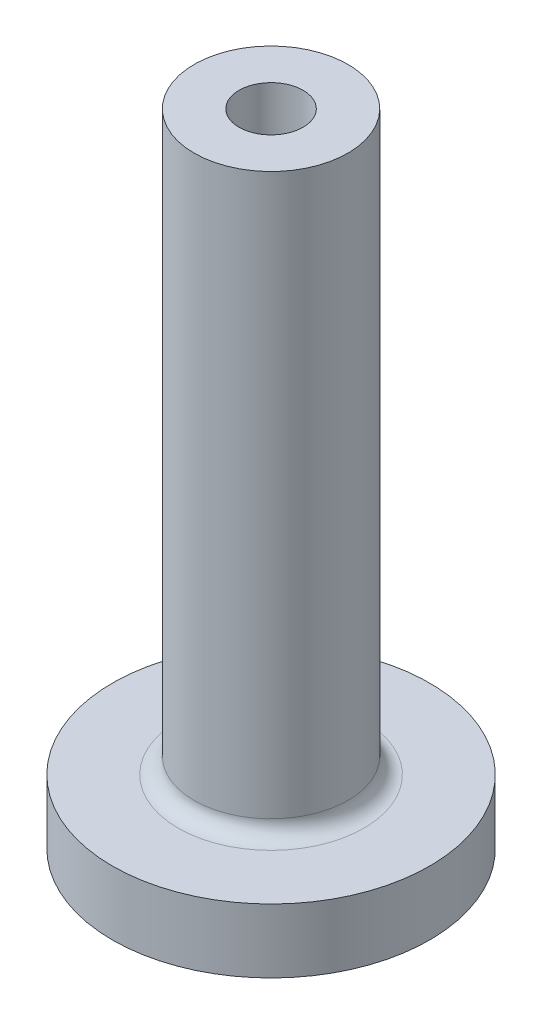
SolidWorks part; units mm, degrees
ref_plane "Front Plane" through (0, 0, 0) normal (0, 0, 1) x (1, 0, 0)
ref_plane "Top Plane" through (0, 0, 0) normal (0, 1, 0) x (1, 0, 0)
ref_plane "Right Plane" through (0, 0, 0) normal (1, 0, 0) x (0, 0, -1)
sketch "Sketch1" plane through (0, 0, 0) normal (0, 1, 0) x (1, 0, 0)
  circle A0 centre (0, 0) radius 9.9
  circle A1 centre (0, 0) radius 4.8
  circle A2 centre (0, 0) radius 2
  dimension "D1" = 4
  dimension "D2" = 9.6
  dimension "D3" = 19.8
extrude "Boss-Extrude1" add sketch "Sketch1" along normal blind 4 contours A2 | A1 A2 | A0 A1 region at (-9.62, 0, 0) region at (-4.6642, 0, 0) region at (0, 0, 0)
extrude "Boss-Extrude2" add sketch "Sketch1<3>" along normal blind 36 from surface contours A2 | A1 A2 region at (-4.6642, 0, 0) region at (0, 0, 0) starting at face at (0, 4, 9.9)
sketch "Sketch1<3>" plane through (0, 0, 0) normal (0, 1, 0) x (1, 0, 0) same geometry as "Sketch1"
extrude "Cut-Extrude1" cut sketch "Sketch1<4>" against normal blind 8 from surface contours A2 region at (0, 0, 0) starting at face at (0, 40, 4.8)
sketch "Sketch1<4>" plane through (0, 0, 0) normal (0, 1, 0) x (1, 0, 0) same geometry as "Sketch1"
fillet "Fillet1" radius 1 1 edges at (0, 4, 4.8)
